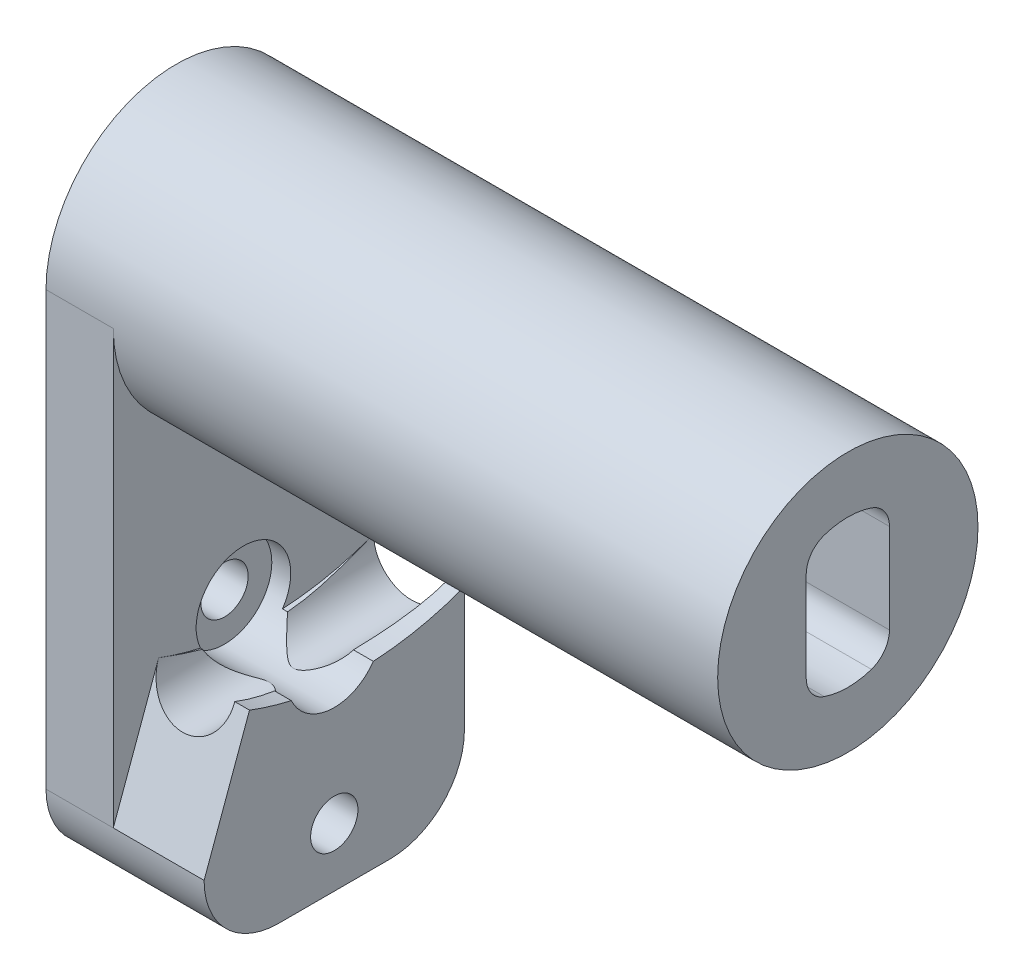
SolidWorks part; units mm, degrees
material "ABS"
ref_plane "Front Plane" through (0, 0, 0) normal (1, 0, 0) x (0, 1, 0)
ref_plane "Top Plane" through (0, 0, 0) normal (0, 0, 1) x (0, 1, 0)
ref_plane "Right Plane" through (0, 0, 0) normal (0, 1, 0) x (-1, 0, 0)
sketch "Sketch1" plane through (0, 0, 0) normal (1, 0, 0) x (0, 1, 0)
  circle A2 centre (0, 0) radius 8.7376
  dimension "D3" = 17.4752
extrude "Boss-Extrude1" add sketch "Sketch1" along normal blind 45.085 contours A2 region at (0, 0, 0)
sketch "Sketch10" plane through (0, 0, 0) normal (-1, 0, 0) x (0, -1, 0)
  line L0 (0, 8.7376) -> (34.036, 8.7376)
  line L2 (34.036, 8.7376) -> (34.036, -8.7376)
  line L3 (34.036, -8.7376) -> (0, -8.7376)
  circle A0 centre (0, 0) radius 8.7376 construction
  arc A2 (0, 8.7376) -> (0, -8.7376) centre (0, 0) cw
  dimension "D1" = 34.036
extrude "Boss-Extrude3" add sketch "Sketch10" against normal blind 4.516 contours L0 A2 L3 L2 region at (0, -20.3793, 0)
fillet "Fillet2" radius 5 2 edges at (2.258, -34.036, 8.7376) (2.258, -34.036, -8.7376)
sketch "Sketch14" [suppressed] plane through (0, 0, 0) normal (-1, 0, 0) x (0, 0, 1)
  line L0 (0.5115, -3.4237) -> (0.3944, -4.0089)
  line L1 (0, 0) -> (0, -4.064) construction
  line L2 (0, 0) -> (0.5606, -3.4335) construction
  line L3 (0.6039, -3.4087) -> (0.9011, -3.9262)
  line L4 (-0.6903, -3.3922) -> (-1.0005, -3.9021)
  line L5 (-0.5983, -3.4096) -> (-0.4961, -3.9976)
  line L6 (-1.8089, -2.9515) -> (-2.2748, -3.3245)
  line L7 (-1.7284, -2.9994) -> (-1.8334, -3.5869)
  line L8 (-2.7093, -2.1549) -> (-3.2746, -2.346)
  line L9 (-2.65, -2.2273) -> (-2.9496, -2.7435)
  line L10 (-3.2829, -1.0983) -> (-3.8795, -1.0846)
  line L11 (-3.252, -1.1867) -> (-3.7101, -1.5692)
  line L12 (-3.4605, 0.0907) -> (-4.0165, 0.3077)
  line L13 (-3.4617, -0.0029) -> (-4.023, -0.2057)
  line L14 (-3.2208, 1.2689) -> (-3.669, 1.6629)
  line L15 (-3.2539, 1.1813) -> (-3.8507, 1.1827)
  line L16 (-2.5926, 2.2939) -> (-2.879, 2.8175)
  line L17 (-2.6537, 2.223) -> (-3.214, 2.4284)
  line L18 (-1.6517, 3.0423) -> (-1.7417, 3.6323)
  line L19 (-1.7333, 2.9965) -> (-2.1896, 3.3812)
  line L20 (-0.5115, 3.4237) -> (-0.3944, 4.0089)
  line L21 (-0.6039, 3.4087) -> (-0.9011, 3.9262)
  line L22 (0.6903, 3.3922) -> (1.0005, 3.9021)
  line L23 (0.5983, 3.4096) -> (0.4961, 3.9976)
  line L24 (1.8089, 2.9515) -> (2.2748, 3.3245)
  line L25 (1.7284, 2.9994) -> (1.8334, 3.5869)
  line L26 (2.7093, 2.1549) -> (3.2746, 2.346)
  line L27 (2.65, 2.2273) -> (2.9496, 2.7435)
  line L28 (3.2829, 1.0983) -> (3.8795, 1.0846)
  line L29 (3.252, 1.1867) -> (3.7101, 1.5692)
  line L30 (3.4605, -0.0907) -> (4.0165, -0.3077)
  line L31 (3.4617, 0.0029) -> (4.023, 0.2057)
  line L32 (3.2208, -1.2689) -> (3.669, -1.6629)
  line L33 (3.2539, -1.1813) -> (3.8507, -1.1827)
  line L34 (2.5926, -2.2939) -> (2.879, -2.8175)
  line L35 (2.6537, -2.223) -> (3.214, -2.4284)
  line L36 (1.6517, -3.0423) -> (1.7417, -3.6323)
  line L37 (1.7333, -2.9965) -> (2.1896, -3.3812)
  line L38 (-0.1032, -4.0627) -> (0, -4.064)
  line L39 (-1.4865, -3.7824) -> (-1.39, -3.8189)
  line L40 (-2.6905, -3.0459) -> (-2.6123, -3.1132)
  line L41 (-3.5195, -2.032) -> (-3.57, -1.942)
  line L42 (-4.0023, -0.7057) -> (-4.0189, -0.6039)
  line L43 (-4.0023, 0.7057) -> (-3.9831, 0.8071)
  line L44 (-3.5195, 2.032) -> (-3.4668, 2.1207)
  line L45 (-2.6123, 3.1132) -> (-2.5324, 3.1785)
  line L46 (-1.39, 3.8189) -> (-1.2926, 3.853)
  line L47 (0, 4.064) -> (0.1032, 4.0627)
  line L48 (1.39, 3.8189) -> (1.4865, 3.7824)
  line L49 (2.6123, 3.1132) -> (2.6905, 3.0459)
  line L50 (3.5195, 2.032) -> (3.57, 1.942)
  line L51 (4.0023, 0.7057) -> (4.0189, 0.6039)
  line L52 (4.0023, -0.7057) -> (3.9831, -0.8071)
  line L53 (3.5195, -2.032) -> (3.4668, -2.1207)
  line L54 (2.6123, -3.1132) -> (2.5324, -3.1785)
  line L55 (1.39, -3.8189) -> (1.2926, -3.853)
  arc A0 (0.3497, -4.0489) -> (0, -4.064) centre (0, 0) cw
  arc A1 (0.3497, -4.0489) -> (0.3944, -4.0089) centre (0.3454, -3.9991) ccw
  arc A2 (0.5115, -3.4237) -> (0.6039, -3.4087) centre (0.5606, -3.4335) cw
  arc A3 (0.4203, -4.0631) -> (0.3944, -4.0089) centre (0.4434, -4.0187) cw
  arc A4 (0.4203, -4.0631) -> (0.7372, -4.2116) centre (2.3016, -0.4608) ccw
  arc A6 (0.9562, -3.9499) -> (0.9011, -3.9262) centre (0.9445, -3.9013) cw
  arc A7 (0.9562, -3.9499) -> (1.2926, -3.853) centre (0, 0) ccw
  arc A8 (-1.0562, -3.9243) -> (-1.39, -3.8189) centre (0, 0) cw
  arc A9 (-1.0562, -3.9243) -> (-1.0005, -3.9021) centre (-1.0432, -3.8761) ccw
  arc A10 (-0.6903, -3.3922) -> (-0.5983, -3.4096) centre (-0.6476, -3.4182) cw
  arc A11 (-0.4524, -4.0387) -> (-0.4961, -3.9976) centre (-0.4468, -3.9891) cw
  arc A12 (-0.4524, -4.0387) -> (-0.1032, -4.0627) centre (0, 0) ccw
  arc A13 (-2.3347, -3.3264) -> (-2.6123, -3.1132) centre (0, 0) cw
  arc A14 (-2.3347, -3.3264) -> (-2.2748, -3.3245) centre (-2.306, -3.2855) ccw
  arc A15 (-1.8089, -2.9515) -> (-1.7284, -2.9994) centre (-1.7776, -2.9906) cw
  arc A16 (-1.8064, -3.6405) -> (-1.8334, -3.5869) centre (-1.7842, -3.5957) cw
  arc A17 (-1.8064, -3.6405) -> (-1.4865, -3.7824) centre (0, 0) ccw
  arc A18 (-3.3316, -2.3273) -> (-3.5195, -2.032) centre (0, 0) cw
  arc A19 (-3.3316, -2.3273) -> (-3.2746, -2.346) centre (-3.2906, -2.2987) ccw
  arc A20 (-2.7093, -2.1549) -> (-2.65, -2.2273) centre (-2.6933, -2.2022) cw
  arc A21 (-2.9426, -2.8031) -> (-2.9496, -2.7435) centre (-2.9064, -2.7686) cw
  arc A22 (-2.9426, -2.8031) -> (-2.6905, -3.0459) centre (0, 0) ccw
  arc A23 (-3.9267, -1.0475) -> (-4.0023, -0.7057) centre (0, 0) cw
  arc A24 (-3.9267, -1.0475) -> (-3.8795, -1.0846) centre (-3.8784, -1.0346) ccw
  arc A25 (-3.2829, -1.0983) -> (-3.252, -1.1867) centre (-3.284, -1.1483) cw
  arc A26 (-3.7238, -1.6276) -> (-3.7101, -1.5692) centre (-3.678, -1.6076) cw
  arc A27 (-3.7238, -1.6276) -> (-3.57, -1.942) centre (0, 0) ccw
  arc A28 (-4.0481, 0.3587) -> (-4.0023, 0.7057) centre (0, 0) cw
  arc A29 (-4.0481, 0.3587) -> (-4.0165, 0.3077) centre (-3.9983, 0.3543) ccw
  arc A30 (-3.4605, 0.0907) -> (-3.4617, -0.0029) centre (-3.4787, 0.0442) cw
  arc A31 (-4.0559, -0.2558) -> (-4.023, -0.2057) centre (-4.006, -0.2527) cw
  arc A32 (-4.0559, -0.2558) -> (-4.0189, -0.6039) centre (0, 0) ccw
  arc A33 (-3.6813, 1.7216) -> (-3.5195, 2.032) centre (0, 0) cw
  arc A34 (-3.6813, 1.7216) -> (-3.669, 1.6629) centre (-3.636, 1.7005) ccw
  arc A35 (-3.2208, 1.2689) -> (-3.2539, 1.1813) centre (-3.2538, 1.2313) cw
  arc A36 (-3.8988, 1.1468) -> (-3.8507, 1.1827) centre (-3.8509, 1.1327) cw
  arc A37 (-3.8988, 1.1468) -> (-3.9831, 0.8071) centre (0, 0) ccw
  arc A38 (-2.8705, 2.8769) -> (-2.6123, 3.1132) centre (0, 0) cw
  arc A39 (-2.8705, 2.8769) -> (-2.879, 2.8175) centre (-2.8352, 2.8415) ccw
  arc A40 (-2.5926, 2.2939) -> (-2.6537, 2.223) centre (-2.6365, 2.2699) cw
  arc A41 (-3.2715, 2.4111) -> (-3.214, 2.4284) centre (-3.2312, 2.3815) cw
  arc A42 (-3.2715, 2.4111) -> (-3.4668, 2.1207) centre (0, 0) ccw
  arc A43 (-1.7134, 3.6852) -> (-1.39, 3.8189) centre (0, 0) cw
  arc A44 (-1.7134, 3.6852) -> (-1.7417, 3.6323) centre (-1.6923, 3.6398) ccw
  arc A45 (-1.6517, 3.0423) -> (-1.7333, 2.9965) centre (-1.7011, 3.0348) cw
  arc A46 (-2.2495, 3.3846) -> (-2.1896, 3.3812) centre (-2.2218, 3.343) cw
  arc A47 (-2.2495, 3.3846) -> (-2.5324, 3.1785) centre (0, 0) ccw
  arc A48 (-0.3497, 4.0489) -> (0, 4.064) centre (0, 0) cw
  arc A49 (-0.3497, 4.0489) -> (-0.3944, 4.0089) centre (-0.3454, 3.9991) ccw
  arc A50 (-0.5115, 3.4237) -> (-0.6039, 3.4087) centre (-0.5606, 3.4335) cw
  arc A51 (-0.9562, 3.9499) -> (-0.9011, 3.9262) centre (-0.9445, 3.9013) cw
  arc A52 (-0.9562, 3.9499) -> (-1.2926, 3.853) centre (0, 0) ccw
  arc A53 (1.0562, 3.9243) -> (1.39, 3.8189) centre (0, 0) cw
  arc A54 (1.0562, 3.9243) -> (1.0005, 3.9021) centre (1.0432, 3.8761) ccw
  arc A55 (0.6903, 3.3922) -> (0.5983, 3.4096) centre (0.6476, 3.4182) cw
  arc A56 (0.4524, 4.0387) -> (0.4961, 3.9976) centre (0.4468, 3.9891) cw
  arc A57 (0.4524, 4.0387) -> (0.1032, 4.0627) centre (0, 0) ccw
  arc A58 (2.3347, 3.3264) -> (2.6123, 3.1132) centre (0, 0) cw
  arc A59 (2.3347, 3.3264) -> (2.2748, 3.3245) centre (2.306, 3.2855) ccw
  arc A60 (1.8089, 2.9515) -> (1.7284, 2.9994) centre (1.7776, 2.9906) cw
  arc A61 (1.8064, 3.6405) -> (1.8334, 3.5869) centre (1.7842, 3.5957) cw
  arc A62 (1.8064, 3.6405) -> (1.4865, 3.7824) centre (0, 0) ccw
  arc A63 (3.3316, 2.3273) -> (3.5195, 2.032) centre (0, 0) cw
  arc A64 (3.3316, 2.3273) -> (3.2746, 2.346) centre (3.2906, 2.2987) ccw
  arc A65 (2.7093, 2.1549) -> (2.65, 2.2273) centre (2.6933, 2.2022) cw
  arc A66 (2.9426, 2.8031) -> (2.9496, 2.7435) centre (2.9064, 2.7686) cw
  arc A67 (2.9426, 2.8031) -> (2.6905, 3.0459) centre (0, 0) ccw
  arc A68 (3.9267, 1.0475) -> (4.0023, 0.7057) centre (0, 0) cw
  arc A69 (3.9267, 1.0475) -> (3.8795, 1.0846) centre (3.8784, 1.0346) ccw
  arc A70 (3.2829, 1.0983) -> (3.252, 1.1867) centre (3.284, 1.1483) cw
  arc A71 (3.7238, 1.6276) -> (3.7101, 1.5692) centre (3.678, 1.6076) cw
  arc A72 (3.7238, 1.6276) -> (3.57, 1.942) centre (0, 0) ccw
  arc A73 (4.0481, -0.3587) -> (4.0023, -0.7057) centre (0, 0) cw
  arc A74 (4.0481, -0.3587) -> (4.0165, -0.3077) centre (3.9983, -0.3543) ccw
  arc A75 (3.4605, -0.0907) -> (3.4617, 0.0029) centre (3.4787, -0.0442) cw
  arc A76 (4.0559, 0.2558) -> (4.023, 0.2057) centre (4.006, 0.2527) cw
  arc A77 (4.0559, 0.2558) -> (4.0189, 0.6039) centre (0, 0) ccw
  arc A78 (3.6813, -1.7216) -> (3.5195, -2.032) centre (0, 0) cw
  arc A79 (3.6813, -1.7216) -> (3.669, -1.6629) centre (3.636, -1.7005) ccw
  arc A80 (3.2208, -1.2689) -> (3.2539, -1.1813) centre (3.2538, -1.2313) cw
  arc A81 (3.8988, -1.1468) -> (3.8507, -1.1827) centre (3.8509, -1.1327) cw
  arc A82 (3.8988, -1.1468) -> (3.9831, -0.8071) centre (0, 0) ccw
  arc A83 (2.8705, -2.8769) -> (2.6123, -3.1132) centre (0, 0) cw
  arc A84 (2.8705, -2.8769) -> (2.879, -2.8175) centre (2.8352, -2.8415) ccw
  arc A85 (2.5926, -2.2939) -> (2.6537, -2.223) centre (2.6365, -2.2699) cw
  arc A86 (3.2715, -2.4111) -> (3.214, -2.4284) centre (3.2312, -2.3815) cw
  arc A87 (3.2715, -2.4111) -> (3.4668, -2.1207) centre (0, 0) ccw
  arc A88 (1.7134, -3.6852) -> (1.39, -3.8189) centre (0, 0) cw
  arc A89 (1.7134, -3.6852) -> (1.7417, -3.6323) centre (1.6923, -3.6398) ccw
  arc A90 (1.6517, -3.0423) -> (1.7333, -2.9965) centre (1.7011, -3.0348) cw
  arc A91 (2.2495, -3.3846) -> (2.1896, -3.3812) centre (2.2218, -3.343) cw
  arc A92 (2.2495, -3.3846) -> (2.5324, -3.1785) centre (0, 0) ccw
  point P207 (0, 0)
  dimension "D1" = 4.064
  dimension "D2" = 0.05
  dimension "D3" = 0.05
  dimension "D4" = 0.04
  dimension "D5" = 18
  dimension "D6" = 0.5968
  dimension "D8" = 0.35
sketch "Sketch15" plane through (4.516, 0, 0) normal (1, 0, 0) x (0, 1, 0)
  line L1 (-29.036, 8.7376) -> (-20.066, 5.4728)
  line L2 (-20.066, 5.4728) -> (-20.066, -8.7376)
  line L5 (-34.036, 3.7376) -> (-34.036, -3.7376) construction
  line L6 (-34.036, 3.7376) -> (-34.036, -3.7376)
  line L9 (-29.036, -8.7376) -> (0, -8.7376) construction
  line L13 (0, 8.7376) -> (-29.036, 8.7376)
  line L14 (-34.036, 3.7376) -> (-34.036, -3.7376)
  line L15 (-29.036, -8.7376) -> (0, -8.7376)
  line L17 (-34.036, 3.7376) -> (-34.036, -3.7376)
  line L18 (-29.036, -8.7376) -> (-20.066, -8.7376)
  arc A0 (-29.036, 8.7376) -> (-34.036, 3.7376) centre (-29.036, 3.7376) ccw construction
  arc A1 (-34.036, -3.7376) -> (-29.036, -8.7376) centre (-29.036, -3.7376) ccw construction
  arc A2 (-29.036, 8.7376) -> (-34.036, 3.7376) centre (-29.036, 3.7376) ccw
  arc A3 (-34.036, -3.7376) -> (-29.036, -8.7376) centre (-29.036, -3.7376) ccw
  arc A7 (-29.036, 8.7376) -> (-34.036, 3.7376) centre (-29.036, 3.7376) ccw
  arc A8 (-34.036, -3.7376) -> (-29.036, -8.7376) centre (-29.036, -3.7376) ccw
  arc A9 (0, 8.7376) -> (0, -8.7376) centre (0, 0) ccw
  arc A10 (-29.036, 8.7376) -> (-34.036, 3.7376) centre (-29.036, 3.7376) ccw
  arc A11 (-34.036, -3.7376) -> (-29.036, -8.7376) centre (-29.036, -3.7376) ccw
  arc A12 (0, 8.7376) -> (0, -8.7376) centre (0, 0) ccw
  line M2 (0, 8.7376) -> (-29.036, 8.7376)
  arc M3 (-29.036, 8.7376) -> (-34.036, 3.7376) centre (-29.036, 3.7376) ccw
  line M4 (-34.036, 3.7376) -> (-34.036, -3.7376)
  arc M5 (-34.036, -3.7376) -> (-29.036, -8.7376) centre (-29.036, -3.7376) ccw
  dimension "D1" = 13.97
  dimension "D3" = 20
  dimension "D2" = 0
extrude "Boss-Extrude4" add sketch "Sketch15" along normal blind 6.096 contours M2 M3 M4 M5 region at (4.516, -27.0306, -0.512)
sketch "Sketch21" plane through (10.612, 0, 0) normal (1, 0, 0) x (0, 1, 0)
  line L2 (-20.066, -8.7376) -> (-20.066, 5.4728)
  line L4 (-29.036, 8.7376) -> (-20.066, 5.4728) construction
  line L5 (-20.701, -8.7376) -> (-20.066, -8.7376)
  line L6 (-20.066, 5.4728) -> (-20.066, -8.7376) construction
  line L7 (-29.036, -8.7376) -> (-20.066, -8.7376) construction
  line L14 (-20.066, -8.7376) -> (-20.066, 5.4728) construction
  line L20 (-20.066, 5.4728) -> (-29.036, 8.7376)
  arc A2 (-20.701, -8.7376) -> (-20.6627, 5.69) centre (-1.6855, -1.5742) cw
  dimension "D4" = 20.32
  dimension "D2" = 0.635
  dimension "D3" = 0.635
extrude "Cut-Extrude8" cut sketch "Sketch21" against normal up to surface (6.096 mm away) contours A2 L2 region at (10.612, -20.8712, -1.5751) up to face at (4.516, -15.5811, 1.0946)
sketch "Sketch22" plane through (45.085, 0, 0) normal (1, 0, 0) x (0, 1, 0)
  line L7 (-4.0897, -2.794) -> (4.0897, 2.794) construction
  line L8 (-4.0897, 2.794) -> (4.0897, -2.794) construction
  line L11 (-4.0897, -2.794) -> (4.0897, -2.794)
  line L13 (-4.0897, 2.794) -> (4.0897, 2.794)
  line L15 (-4.0897, -2.794) -> (4.0897, 2.794) construction
  line L16 (-4.0897, 2.794) -> (4.0897, -2.794) construction
  arc A3 (-4.0897, 2.794) -> (-4.0897, -2.794) centre (0, 0) ccw
  arc A4 (4.0897, -2.794) -> (4.0897, 2.794) centre (0, 0) ccw
  dimension "D2" = 9.906
  dimension "D3" = 5.588
extrude "Cut-Extrude10" cut sketch "Sketch22" against normal blind 12.192
sketch "Sketch23" plane through (0, 0, 0) normal (-1, 0, 0) x (0, 0, 1)
  line L0 (0, -33.5187) -> (0, 0) construction
  line L2 (0, -30.0897) -> (0, -20.1843) construction
  line L3 (0, -20.1843) -> (0, -10.279) construction
  line L6 (-3.7376, -33.5187) -> (3.7376, -33.5187)
  line L7 (8.2296, -29.0267) -> (8.2296, 0)
  line L8 (-8.2296, 0) -> (-8.2296, -29.0267)
  arc A6 (-8.2296, -29.0267) -> (-3.7376, -33.5187) centre (-3.7376, -29.0267) ccw
  arc A7 (3.7376, -33.5187) -> (8.2296, -29.0267) centre (3.7376, -29.0267) ccw
  arc A8 (8.2296, 0) -> (-8.2296, 0) centre (0, 0) ccw
  circle A9 centre (0, -30.0897) radius 1.5875
  circle A10 centre (0, -20.1843) radius 1.5875
  dimension "D1" = 3.175
  dimension "D3" = 4.492
  dimension "D5" = 8.2296
  dimension "D2" = 9.9054
  dimension "D4" = 29.0267
  dimension "D6" = 3.429
extrude "Cut-Extrude11" cut sketch "Sketch23" against normal through all contours A10 | A9 region at (0, -30.0897, 0) region at (0, -20.1843, 0)
sketch "Sketch24" plane through (4.516, 0, 0) normal (1, 0, 0) x (0, 1, 0)
  circle A0 centre (-20.1843, 0) radius 1.5875 construction
  circle A1 centre (-20.1843, 0) radius 1.5875
  circle A2 centre (-20.1843, 0) radius 3.175
  dimension "D1" = 6.35
extrude "Cut-Extrude12" cut sketch "Sketch24" along normal through all
extrude "Cut-Extrude13" cut sketch "Sketch24<2>" against normal blind 1.27
sketch "Sketch24<2>" plane through (4.516, 0, 0) normal (1, 0, 0) x (0, 1, 0) same geometry as "Sketch24"
fillet "Fillet11" radius 1.778 4 edges at (38.989, 4.0897, -2.794) (38.989, 4.0897, 2.794) (38.989, -4.0897, -2.794) (38.989, -4.0897, 2.794)
sketch "Sketch25" plane through (0, 0, -8.7376) normal (0, 0, -1) x (1, 0, 0)
  line L3 (4.516, 20.701) -> (4.516, 0) construction
  line L4 (4.516, 20.701) -> (10.612, 20.701) construction
  circle A0 centre (7.0687, 20.701) radius 2.5527
  dimension "D1" = 5.1054
extrude "Cut-Extrude14" cut sketch "Sketch25" against normal through all
